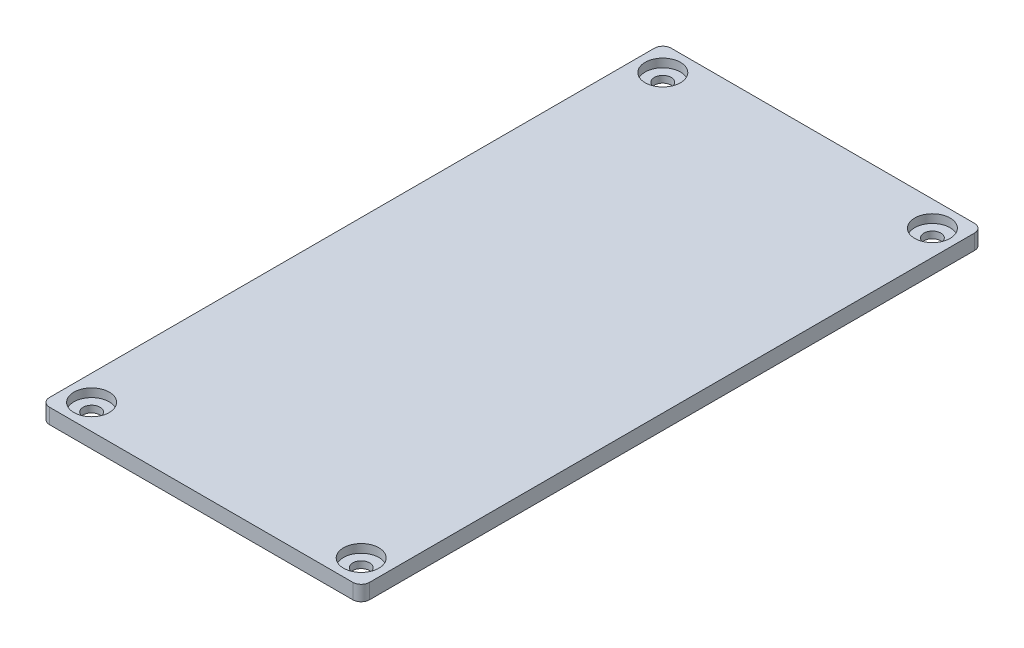
SolidWorks part; units mm, degrees
ref_plane "Front Plane" through (0, 0, 0) normal (0, 0, 1) x (1, 0, 0)
ref_plane "Top Plane" through (0, 0, 0) normal (0, 1, 0) x (1, 0, 0)
ref_plane "Right Plane" through (0, 0, 0) normal (1, 0, 0) x (0, 0, -1)
ref_axis "X-Axis" through (-88.99, 0, 0) along (1, 0, 0)
ref_axis "Y-Axis" through (0, 55, 0) along (0, -1, 0)
ref_axis "Z-Axis" through (0, 0, -88.99) along (0, 0, 1)
sketch "Sketch1" plane through (0, 0, 0) normal (0, 1, 0) x (1, 0, 0)
  line L1 (-19, -36.9) -> (19, -36.9)
  line L2 (-19, -36.9) -> (-19, 36.9)
  line L3 (-19, 36.9) -> (19, 36.9)
  line L4 (19, -36.9) -> (19, 36.9)
  line L5 (-19, -36.9) -> (19, 36.9) construction
  line L6 (-19, 36.9) -> (19, -36.9) construction
  point P0 (0, 0)
  dimension "D1" = 73.8
  dimension "D2" = 38
extrude "Boss-Extrude1" add sketch "Sketch1" along normal blind 1.8
sketch "Sketch2" plane through (0, 1.8, 0) normal (0, 1, 0) x (1, 0, 0)
  line L0 (-19, 33.9) -> (19, 33.9) construction
  line L1 (-19, 36.9) -> (-19, -36.9) construction
  line L2 (19, -36.9) -> (19, 36.9) construction
  line L3 (19, 36.9) -> (-19, 36.9) construction
  circle A0 centre (-16, 33.9) radius 1
  circle A1 centre (16, 33.9) radius 1
  dimension "D2" = 2
  dimension "D1" = 3
  dimension "D3" = 3
  dimension "D4" = 3
extrude "Cut-Extrude1" cut sketch "Sketch2" against normal through all
sketch "Sketch3" plane through (0, 1.8, 0) normal (0, 1, 0) x (1, 0, 0)
  circle A0 centre (-16, 33.9) radius 2.1
  circle A1 centre (16, 33.9) radius 2.1
  dimension "D1" = 4.2
extrude "Cut-Extrude2" cut sketch "Sketch3" against normal blind 1
mirror "Mirror1" about plane through (0, 0, 0) normal (0, 0, 1) of "Cut-Extrude2", "Cut-Extrude1"
fillet "Fillet1" radius 1 4 edges at (-19, 0.9, -36.9) (19, 0.9, -36.9) (19, 0.9, 36.9) (-19, 0.9, 36.9)
equation "\"D4@Sketch2\"=\"D1@Sketch2\""
